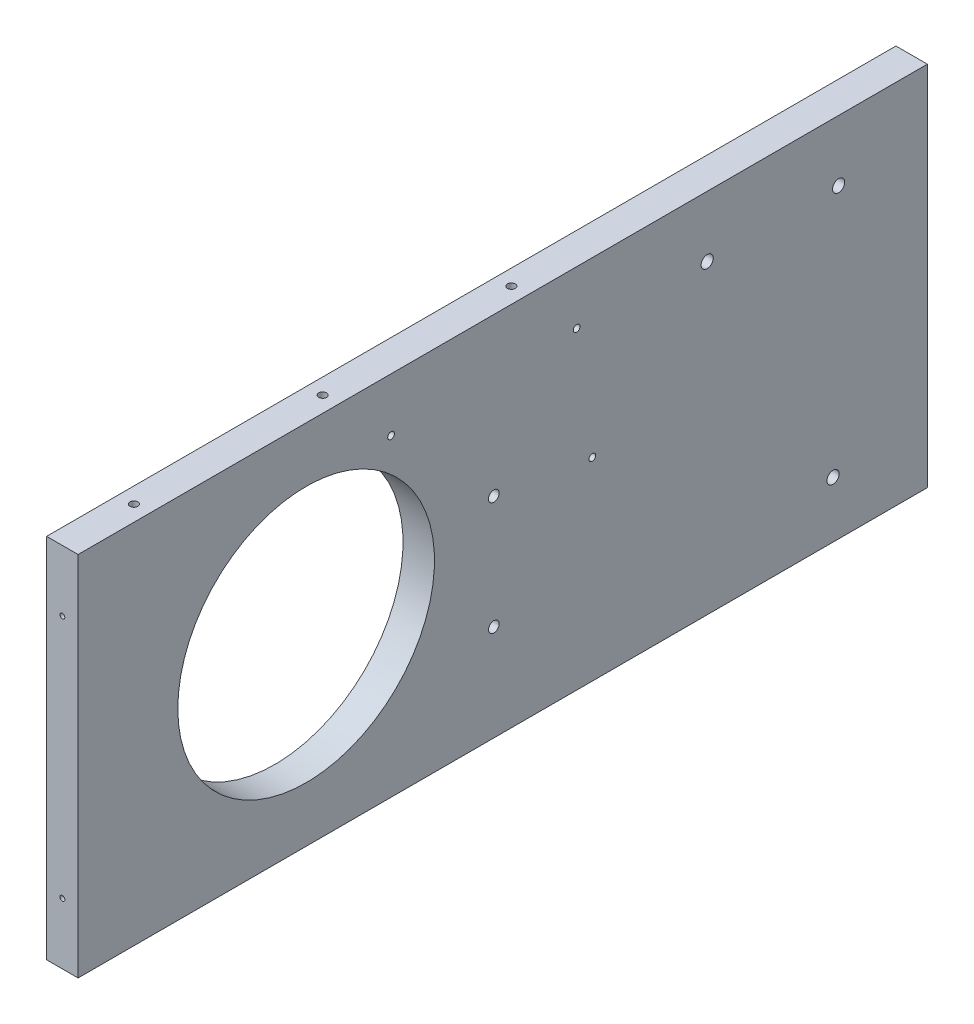
SolidWorks part; units mm, degrees
material "MDF"
ref_plane "Front Plane" through (0, 0, 0) normal (0, 0, 1) x (1, 0, 0)
ref_plane "Top Plane" through (0, 0, 0) normal (0, 1, 0) x (1, 0, 0)
ref_plane "Right Plane" through (0, 0, 0) normal (1, 0, 0) x (0, 0, -1)
sketch "Sketch1" plane through (0, 0, 0) normal (0, 0, 1) x (1, 0, 0)
  line L0 (-272.8912, -3.175) -> (-450.3737, -3.175) construction
  line L1 (-438.8802, -3.175) -> (-451.5802, -3.175)
  line L2 (-438.8802, -3.175) -> (-438.8802, -151.2545)
  line L3 (-438.8802, -151.2545) -> (-451.5802, -151.2545)
  line L4 (-451.5802, -3.175) -> (-451.5802, -151.2545)
  line L6 (-450.3737, -152.2395) -> (-393.0861, -199.0142) construction
  line L8 (-451.5802, -20.574) -> (-451.5802, -45.974) construction
  dimension "D1" = 12.7
extrude "Boss-Extrude1" add sketch "Sketch1" along normal blind 342.9
hole_wizard "15/64 (0.23438) Diameter Hole1" positions "Sketch2" profile "Sketch3" hole size "15/64" standard "ANSI Inch"
sketch "Sketch2" plane through (-183.6737, 1933.3759, -6.35) normal (0, 0, -1) x (1, 0, 0)
  point P0 (-261.5565, 1973.5707)
  point P3 (-261.5565, 2010.5906)
  point P6 (-261.5565, 2047.6104)
  point P9 (-97.5233, 2112.4817)
  point P12 (-97.5233, 2147.6884)
  point P15 (-43.3641, 2120.0659)
  point P18 (1.27, 2120.0659)
  point P21 (45.9041, 2120.0659)
  point P24 (100.0633, 2147.6884)
  point P27 (100.0633, 2112.4817)
  point P30 (264.0965, 2047.6104)
  point P33 (264.0965, 1973.5707)
sketch "Sketch3" plane through (-445.2302, -40.1949, -6.35) normal (1, 0, 0) x (0, 1, 0)
  line L0 (0, 0) -> (0, 14.4885)
  line L1 (0, 14.4885) -> (2.9766, 12.7)
  line L2 (2.9766, 12.7) -> (2.9766, 0)
  line L3 (2.9766, 0) -> (0, 0)
  line L4 (0, 14.4885) -> (-2.9766, 12.7) construction
  line L5 (0, -6.35) -> (0, 107.95) construction
  dimension "Hole Dia." = 5.9533
  dimension "Hole Depth" = 12.7
  dimension "Drill Angle" = 118
hole_wizard "15/64 (0.23438) Diameter Hole3" positions "Sketch6" profile "Sketch7" hole size "15/64" standard "ANSI Inch"
sketch "Sketch6" plane through (-182.4037, 1936.854, -6.35) normal (0, 0, -1) x (1, 0, 0)
  point P0 (-262.8265, 2051.0885)
  point P3 (-262.8265, 2014.0687)
  point P6 (-262.8265, 1977.0488)
  point P9 (-98.7933, 2115.9598)
  point P12 (-98.7933, 2151.1665)
sketch "Sketch7" plane through (-445.2302, -114.2346, -6.35) normal (1, 0, 0) x (0, 1, 0)
  line L0 (0, 0) -> (0, 20.8385)
  line L1 (0, 20.8385) -> (2.9766, 19.05)
  line L2 (2.9766, 19.05) -> (2.9766, 0)
  line L3 (2.9766, 0) -> (0, 0)
  line L4 (0, 20.8385) -> (-2.9766, 19.05) construction
  line L5 (0, -6.35) -> (0, 107.95) construction
  dimension "Hole Dia." = 5.9533
  dimension "Hole Depth" = 19.05
  dimension "Drill Angle" = 118
hole_wizard "5/64 (0.07813) Diameter Hole1" positions "Sketch8" profile "Sketch9" hole size "5/64" standard "ANSI Inch"
sketch "Sketch8" plane through (-182.4037, 15.875, 6471.4599) normal (0, 1, 0) x (1, 0, 0)
  line L1 (-1.27, 6109.5099) -> (-1.27, 6338.7449) construction
  point P0 (-262.8265, 6157.4524)
  point P6 (-98.7933, 6157.4524)
  point P18 (-262.8265, 6233.6524)
  point P19 (-98.7933, 6233.6524)
  point P22 (-262.8265, 6309.8524)
  point P23 (-98.7933, 6309.8524)
  point P24 (-267.97, 6119.0349)
  point P34 (-115.57, 6119.0349)
  point P37 (-1.27, 6119.0349)
  point P40 (113.03, 6119.0349)
  point P44 (265.43, 6119.0349)
  point P55 (98.7933, 6309.8524)
  point P56 (262.8265, 6309.8524)
  point P59 (98.7933, 6233.6524)
  point P60 (262.8265, 6233.6524)
  point P63 (98.7933, 6157.4524)
  point P64 (262.8265, 6157.4524)
  point P111 (0, 0)
  point P112 (0, 0)
  point P113 (0, 0)
  point P114 (0, 0)
sketch "Sketch9" plane through (-445.2302, 15.875, 314.0075) normal (1, 0, 0) x (0, 0, 1)
  line L0 (0, 0) -> (0, 39.0539)
  line L1 (0, 39.0539) -> (1.5875, 38.1)
  line L2 (1.5875, 38.1) -> (1.5875, 4.0177)
  line L3 (1.5875, 4.0177) -> (5.08, 0)
  line L4 (5.08, 0) -> (0, 0)
  line L5 (-1.5875, 4.0177) -> (-5.08, 0) construction
  line L6 (0, 39.0539) -> (-1.5875, 38.1) construction
  line L7 (0, -6.35) -> (0, 107.95) construction
  dimension "Hole Dia." = 3.175
  dimension "Hole Depth" = 38.1
  dimension "Near C'Sink Dia." = 10.16
  dimension "Near C'Sink Angle" = 82
  dimension "Drill Angle" = 118
hole_wizard "5/64 (0.07813) Diameter Hole2" positions "Sketch10" profile "Sketch11" hole size "5/64" standard "ANSI Inch"
sketch "Sketch10" plane through (-182.4037, 1936.854, 361.95) normal (0, 0, 1) x (-1, 0, 0)
  line L23 (262.8265, 2088.1084) -> (262.8265, 2038.7486)
  line L24 (262.8265, 2038.7486) -> (262.8265, 1989.3888)
  line L25 (262.8265, 1989.3888) -> (262.8265, 2038.7486)
  line L26 (262.8265, 2038.7486) -> (262.8265, 1989.3888)
  line L27 (262.8265, 1989.3888) -> (262.8265, 1940.029)
  line L33 (98.7933, 2170.2165) -> (98.7933, 2131.8519)
  line L35 (98.7933, 2131.8519) -> (98.7933, 2093.4873)
  line L36 (98.7933, 2093.4873) -> (98.7933, 2055.1227)
  line L37 (98.7933, 2055.1227) -> (98.7933, 2016.7581)
  line L38 (98.7933, 2016.7581) -> (98.7933, 1978.3935)
  line L39 (98.7933, 1978.3935) -> (98.7933, 1940.029)
  line L44 (89.2683, 2123.544) -> (53.561, 2123.544)
  line L46 (53.561, 2123.544) -> (17.8537, 2123.544)
  line L47 (17.8537, 2123.544) -> (-17.8537, 2123.544)
  line L48 (-17.8537, 2123.544) -> (-53.561, 2123.544)
  line L49 (-53.561, 2123.544) -> (-89.2683, 2123.544)
  line L53 (0, 2170.2165) -> (-0.3175, 1940.029) construction
  line L55 (-99.3221, 1978.6668) -> (-99.4279, 1940.3024)
  line L56 (-99.2163, 2017.0312) -> (-99.3221, 1978.6668)
  line L57 (-99.1104, 2055.3957) -> (-99.2163, 2017.0312)
  line L58 (-99.0046, 2093.7601) -> (-99.1104, 2055.3957)
  line L59 (-98.8988, 2132.1245) -> (-99.0046, 2093.7601)
  line L60 (-98.7929, 2170.489) -> (-98.8988, 2132.1245)
  line L61 (-263.3243, 1990.1145) -> (-263.4605, 1940.7549)
  line L62 (-263.1882, 2039.4741) -> (-263.3243, 1990.1145)
  line L63 (-263.3243, 1990.1145) -> (-263.1882, 2039.4741)
  line L64 (-263.1882, 2039.4741) -> (-263.3243, 1990.1145)
  line L65 (-263.052, 2088.8338) -> (-263.1882, 2039.4741)
  point P71 (262.8265, 1964.7089)
  point P79 (262.8265, 2063.4285)
  point P95 (98.7933, 2131.8519)
  point P103 (98.7933, 1978.3935)
  point P126 (53.561, 2123.544)
  point P134 (-53.561, 2123.544)
  point P162 (-98.7933, 1978.3935)
  point P166 (-98.7933, 2131.8519)
  point P167 (-262.8265, 2063.4285)
  point P169 (-262.8265, 1964.7089)
  point P184 (0, 0)
  point P185 (0, 0)
  point P186 (0, 0)
  point P189 (0, 0)
  point P192 (0, 0)
  point P195 (0, 0)
sketch "Sketch11" plane through (80.4228, -27.8549, 361.95) normal (1, 0, 0) x (0, -1, 0)
  line L0 (0, 0) -> (0, 38.6962)
  line L1 (0, 38.6962) -> (0.9923, 38.1)
  line L2 (0.9923, 38.1) -> (0.9923, 4.7024)
  line L3 (0.9923, 4.7024) -> (5.08, 0)
  line L4 (5.08, 0) -> (0, 0)
  line L5 (-0.9923, 4.7024) -> (-5.08, 0) construction
  line L6 (0, 38.6962) -> (-0.9923, 38.1) construction
  line L7 (0, -6.35) -> (0, 107.95) construction
  dimension "Hole Dia." = 1.9845
  dimension "Hole Depth" = 38.1
  dimension "Near C'Sink Dia." = 10.16
  dimension "Near C'Sink Angle" = 82
  dimension "Drill Angle" = 118
hole_wizard "#8 Clearance Hole1" positions "Sketch12" profile "Sketch13" hole size "#8" standard "ANSI Inch" end condition up to next
sketch "Sketch12" plane through (-451.5802, 0, 0) normal (-1, 0, 0) x (0, 0, 1)
  point P0 (88.9, -27.7495)
  point P2 (35.8275, -27.7495)
  point P4 (38.1, -128.5875)
sketch "Sketch13" plane through (-451.5802, -27.7495, 88.9) normal (0, 1, 0) x (0, 0, 1)
  line L0 (0, 0) -> (0, 12.7)
  line L1 (0, 12.7) -> (2.4574, 12.7)
  line L2 (2.4574, 12.7) -> (2.4574, 0)
  line L5 (2.4574, 0) -> (0, 0)
  line L11 (0, -6.35) -> (0, 107.95) construction
  dimension "Thru Hole Dia." = 4.9149
  dimension "Thru Hole Depth" = 12.7
sketch "Sketch14" plane through (-451.5802, 0, 0) normal (-1, 0, 0) x (0, 0, 1)
  line L0 (158.75, -33.3375) -> (342.9, -33.3375) construction
  line L1 (158.75, -53.975) -> (158.75, -12.7) construction
  line L2 (342.9, -3.175) -> (342.9, -151.2545) construction
  line L3 (250.825, -151.2545) -> (250.825, -3.175) construction
  line L4 (342.9, -151.2545) -> (0, -151.2545) construction
  line L5 (132.715, -3.175) -> (361.95, -3.175) construction
  circle A0 centre (250.825, -77.2147) radius 51.8147
  point P6 (250.825, -33.3375)
  point P13 (250.825, -77.2147)
  point P16 (250.825, -129.0295)
  dimension "D1" = 22.225
extrude "Cut-Extrude1" cut sketch "Sketch14" against normal up to next
hole_wizard "#6 Clearance Hole1" positions "Sketch15" profile "Sketch16" hole size "#6" standard "ANSI Inch" end condition up to next
sketch "Sketch15" plane through (-438.8802, 0, 0) normal (1, 0, 0) x (0, 0, -1)
  point P0 (-175.0568, -66.675)
  point P3 (-175.0568, -112.395)
sketch "Sketch16" plane through (-438.8802, -66.675, 175.0568) normal (0, 1, 0) x (0, 0, -1)
  line L0 (0, 0) -> (0, 12.7)
  line L1 (0, 12.7) -> (2.1526, 12.7)
  line L2 (2.1526, 12.7) -> (2.1526, 0)
  line L5 (2.1526, 0) -> (0, 0)
  line L11 (0, -6.35) -> (0, 107.95) construction
  dimension "Thru Hole Dia." = 4.3053
  dimension "Thru Hole Depth" = 12.7
hole_wizard "#2 Clearance Hole1" positions "Sketch17" profile "Sketch18" hole size "#2" standard "ANSI Inch" end condition up to next
sketch "Sketch17" plane through (-438.8802, 0, 0) normal (1, 0, 0) x (0, 0, -1)
  point P0 (-216.5404, -24.765)
  point P3 (-141.6104, -24.765)
  point P6 (-135.2604, -73.025)
sketch "Sketch18" plane through (-438.8802, -24.765, 216.5404) normal (0, 1, 0) x (0, 0, -1)
  line L0 (0, 0) -> (0, 12.7)
  line L1 (0, 12.7) -> (1.3525, 12.7)
  line L2 (1.3525, 12.7) -> (1.3525, 0)
  line L5 (1.3525, 0) -> (0, 0)
  line L11 (0, -6.35) -> (0, 107.95) construction
  dimension "Thru Hole Dia." = 2.7051
  dimension "Thru Hole Depth" = 12.7
